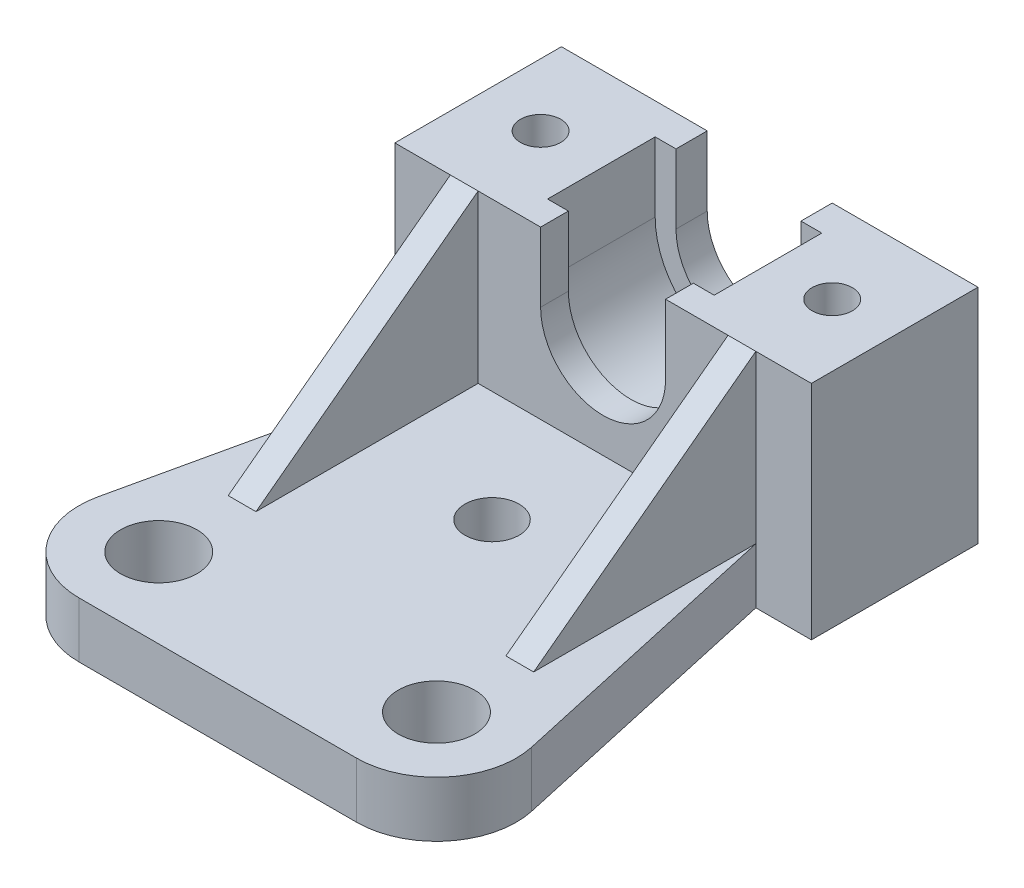
SolidWorks part; units mm, degrees
ref_plane "Front Plane" through (0, 0, 0) normal (0, 0, 1) x (1, 0, 0)
ref_plane "Top Plane" through (0, 0, 0) normal (0, 1, 0) x (1, 0, 0)
ref_plane "Right Plane" through (0, 0, 0) normal (1, 0, 0) x (0, 0, -1)
sketch "Sketch1" plane through (0, 0, 0) normal (0, 0, 1) x (1, 0, 0)
  line L0 (-5.2806, 25) -> (-5.2806, 41)
  line L2 (-5.2806, 41) -> (5.2194, 41)
  line L3 (24.7194, 41) -> (24.7194, 25)
  line L5 (24.7194, 25) -> (9.7194, 25)
  line L9 (9.7194, 25) -> (-5.2806, 25)
  line L10 (9.7194, 25) -> (9.7194, 47) construction
  line L11 (14.2194, 41) -> (24.7194, 41)
  line L13 (5.2194, 36) -> (5.2194, 41)
  line L15 (14.2194, 36) -> (14.2194, 41)
  arc A0 (5.2194, 36) -> (14.2194, 36) centre (9.7194, 36) ccw
  dimension "D3" = 4.5
  dimension "D4" = 16
  dimension "D5" = 30
  dimension "D6" = 5
extrude "Boss-Extrude1" add sketch "Sketch1" against normal blind 12 contours L13 L2 L0 L9 L5 L3 L11 L15 A0
sketch "Sketch2" plane through (0, 0, 0) normal (0, 0, 1) x (1, 0, 0)
  line L0 (14.2194, 41) -> (24.7194, 41) construction
  line L2 (3.7194, 36) -> (3.7194, 41)
  line L3 (3.7194, 41) -> (15.7194, 41)
  line L4 (15.7194, 36) -> (15.7194, 41)
  arc A0 (3.7194, 36) -> (15.7194, 36) centre (9.7194, 36) ccw
  dimension "D1" = 12
extrude "Cut-Extrude1" cut sketch "Sketch2" against normal blind 7.75 from offset 2 offset against normal yes
sketch "Sketch3" plane through (0, 41, 0) normal (0, 1, 0) x (1, 0, 0)
  line L0 (24.7194, 6) -> (-5.2806, 6) construction
  line L1 (24.7194, 12) -> (24.7194, 0) construction
  line L2 (-5.2806, 12) -> (-5.2806, 0) construction
  line L3 (5.2194, 12) -> (14.2194, 12) construction
  line L4 (9.7194, 12) -> (9.7194, 0) construction
  circle A0 centre (20.2194, 6) radius 1.45
  circle A1 centre (-0.7806, 6) radius 1.45
  dimension "D2" = 2.9
  dimension "D1" = 4.5
extrude "Cut-Extrude2" cut sketch "Sketch3" against normal blind 18
sketch "Sketch4" plane through (0, 0, 0) normal (0, 0, 1) x (1, 0, 0)
  line L0 (-1.2806, 25) -> (-1.2806, 29)
  line L1 (24.7194, 25) -> (-5.2806, 25) construction
  line L2 (-1.2806, 29) -> (20.7194, 29)
  line L8 (-1.2806, 25) -> (20.7194, 25)
  line L10 (20.7194, 25) -> (20.7194, 29)
  dimension "D2" = 4
extrude "Boss-Extrude2" add sketch "Sketch4" along normal blind 16
sketch "Sketch5" plane through (0, 29, 0) normal (0, 1, 0) x (1, 0, 0)
  line L0 (9.7194, -16) -> (9.7194, 0) construction
  line L1 (20.7194, -16) -> (-1.2806, -16) construction
  line L2 (20.7194, 0) -> (-1.2806, 0) construction
  circle A0 centre (9.7194, -8) radius 1.95
  dimension "D1" = 3.9
  dimension "D3" = 8
extrude "Cut-Extrude3" cut sketch "Sketch5" against normal mid plane 29
sketch "Sketch6" plane through (-1.2806, 0, 0) normal (-1, 0, 0) x (0, 0, 1)
  line L0 (16, 29) -> (0, 41)
  line L1 (0, 41) -> (0, 29)
  line L2 (0, 29) -> (16, 29)
extrude "Boss-Extrude3" add sketch "Sketch6" against normal blind 2
extrude "Boss-Extrude4" add sketch "Sketch6<2>" along normal blind 2 from offset 22 offset against normal yes
sketch "Sketch6<2>" plane through (-1.2806, 0, 0) normal (-1, 0, 0) x (0, 0, 1) same geometry as "Sketch6"
sketch "Sketch7" plane through (0, 25, 0) normal (0, -1, 0) x (-1, 0, 0)
  line L0 (1.2806, 0) -> (5.8936, -20.7523)
  line L1 (0.2806, -27.75) -> (-19.7194, -27.75)
  line L2 (-9.7194, -27.75) -> (-9.7194, 12) construction
  line L3 (-24.7194, 12) -> (5.2806, 12) construction
  line L4 (1.2806, 0) -> (1.2806, -16)
  line L5 (1.2806, -16) -> (-20.7194, -16)
  line L6 (1.2806, -16) -> (-20.7194, -16) construction
  line L7 (-20.7194, 0) -> (-20.7194, -16)
  line L8 (-20.7194, 0) -> (-25.3324, -20.7523)
  line L9 (-24.7194, 0) -> (-20.7194, 0) construction
  arc A0 (0.2806, -27.75) -> (5.8936, -20.7523) centre (0.2806, -22) ccw
  arc A1 (-19.7194, -27.75) -> (-25.3324, -20.7523) centre (-19.7194, -22) cw
  circle A2 centre (0.2806, -22) radius 2.75
  circle A3 centre (-19.7194, -22) radius 2.75
  point P19 (-9.7194, -16)
  dimension "D2" = 5.5
  dimension "D3" = 3
  dimension "D1" = 20
  dimension "D4" = 22
extrude "Boss-Extrude5" add sketch "Sketch7" against normal blind 4
